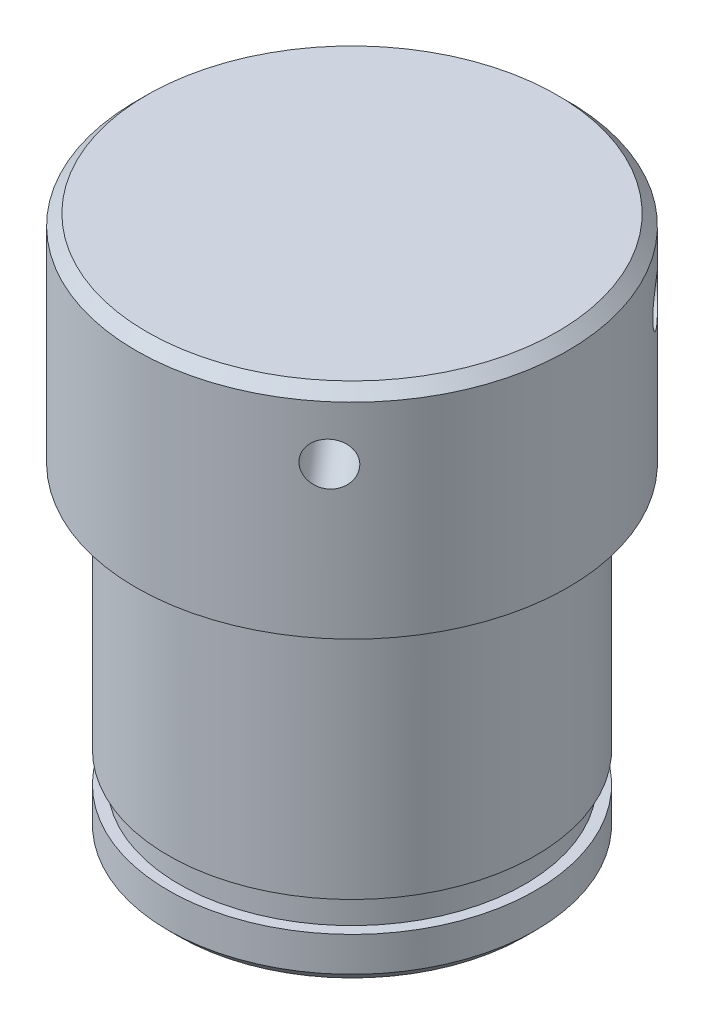
SolidWorks part; units mm, degrees
material "ABS"
ref_plane "Спереди" through (0, 0, 0) normal (0, 0, 1) x (1, 0, 0)
ref_plane "Сверху" through (0, 0, 0) normal (0, 1, 0) x (1, 0, 0)
ref_plane "Справа" through (0, 0, 0) normal (1, 0, 0) x (0, 0, -1)
sketch "Эскиз1" plane through (0, 0, 0) normal (0, 1, 0) x (1, 0, 0)
  circle A0 centre (0, 0) radius 8.5
  dimension "D1" = 17
extrude "Бобышка-Вытянуть1" add sketch "Эскиз1" along normal blind 15
sketch "Эскиз2" plane through (0, 15, 0) normal (0, 1, 0) x (1, 0, 0)
  circle A0 centre (0, 0) radius 10
  dimension "D1" = 20
extrude "Бобышка-Вытянуть2" add sketch "Эскиз2" along normal blind 10
sketch "Эскиз3" plane through (0, 0, 0) normal (0, -1, 0) x (1, 0, 0)
  circle A0 centre (0, 6) radius 1
  circle A1 centre (6, 0) radius 1
  circle A2 centre (0, -6) radius 1
  circle A3 centre (-6, 0) radius 1
  point P12 (0, 0)
  dimension "D1" = 2
  dimension "D2" = 6
  dimension "D3" = 4
extrude "Вырез-Вытянуть1" cut sketch "Эскиз3" against normal blind 10
sketch "Эскиз4" plane through (0, 0, 0) normal (0, -1, 0) x (1, 0, 0)
  circle A0 centre (0, 0) radius 8
  circle A1 centre (0, 0) radius 8.5
  dimension "D1" = 16
extrude "Вырез-Вытянуть2" cut sketch "Эскиз4" against normal blind 1.4 from offset 2.1 offset against normal yes
chamfer "Фаска1" distance 0.5 angle 45 2 edges at (0, 0, 8.5) (0, 25, 10)
sketch "Эскиз6" plane through (0, 25, 0) normal (0, 1, 0) x (1, 0, 0)
  line L0 (0, 12.2337) -> (0, -13.1957) construction
ref_plane "Плоскость1" through (6.5246, 0, 7.5782) normal (0.6525, 0, 0.7578) x (0.7578, 0, -0.6525)
sketch "Эскиз7" plane through (6.5246, 0, 7.5782) normal (0.6525, 0, 0.7578) x (0.7578, 0, -0.6525)
  line L0 (7.982, 25) -> (-8.6096, 25) construction
  circle A0 centre (0, 22) radius 1
  dimension "D1" = 2
  dimension "D2" = 3
extrude "Вырез-Вытянуть3" cut sketch "Эскиз7" against normal blind 8
pattern_circular "Круговой массив1" count 4 over 360 about axis through (0, 25, 0) along (0, -1, 0) of "Вырез-Вытянуть3"
sketch "Эскиз8" plane through (0, 0, 0) normal (0, -1, 0) x (1, 0, 0)
  circle A0 centre (0, 0) radius 3.5
  dimension "D1" = 7
extrude "Вырез-Вытянуть4" cut sketch "Эскиз8" against normal blind 5.5
chamfer "Фаска2" distance 0.5 angle 45 1 edges at (0, 0, -3.5)
